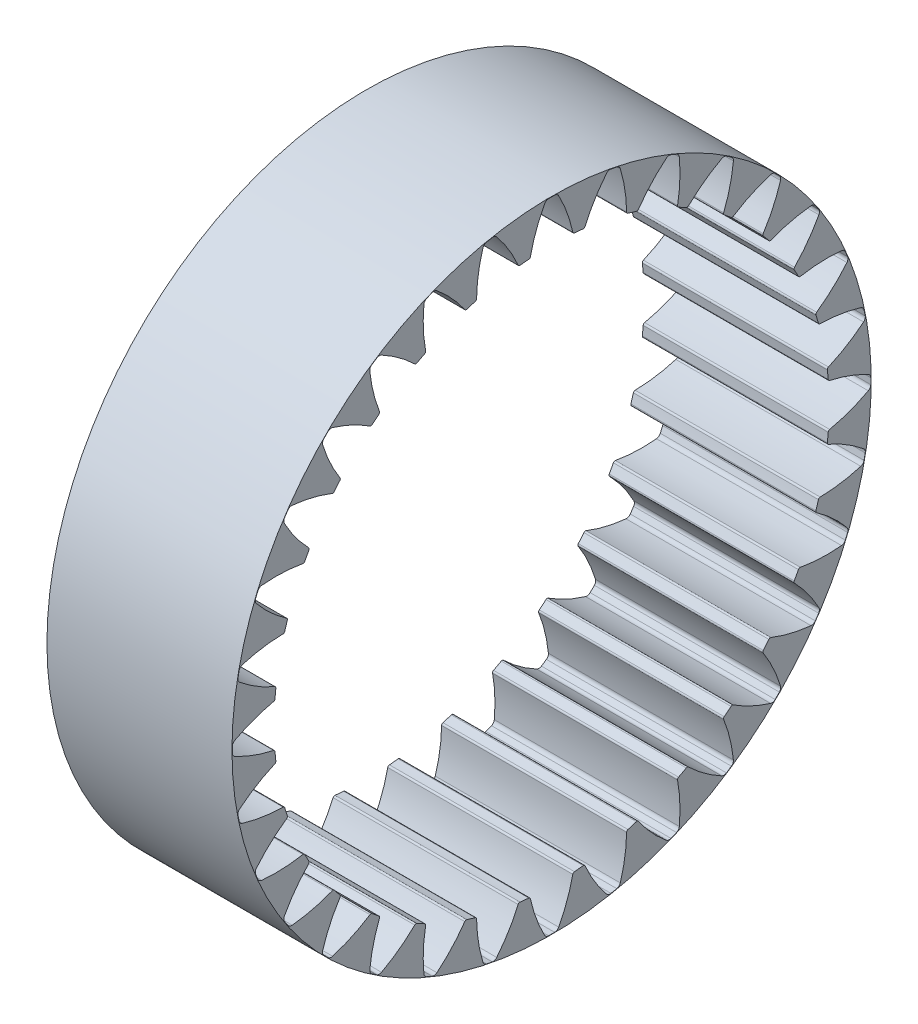
SolidWorks part; units mm, degrees
ref_plane "Plane1" through (0, 0, 0) normal (0, 0, 1) x (1, 0, 0)
ref_plane "Plane2" through (0, 0, 0) normal (0, 1, 0) x (1, 0, 0)
ref_plane "Plane3" through (0, 0, 0) normal (1, 0, 0) x (0, 0, -1)
sketch "HoldingSke" plane through (0, 0, 0) normal (0, 1, 0) x (1, 0, 0)
  line L0 (0, 0) -> (0.848, -0.5299)
  line L1 (-15, 0) -> (100, 0) construction
  line L2 (0, 0) -> (-2.1039, 2.3779)
  line L3 (0, 0) -> (-11.863, 4.5341)
  line L4 (0, 0) -> (7.3237, 4.5764)
  line L5 (0, 0) -> (-23.7986, -8.8762)
  line L6 (0, 0) -> (-10.5278, -7.1032)
  line L7 (-2.1039, 2.3779) -> (3.3635, 27.1825)
  line L8 (-76.2, 3.3779) -> (-54.61, 3.3779)
  line L9 (-67.7845, 28.3722) -> (-49.3413, 33.142)
  line L10 (-76.2, 71.12) -> (104.1128, 71.12)
  line L11 (0, 0) -> (-10, 0)
  line L12 (-76.2, 101.6) -> (-76.162, 101.6)
  line L13 (24.9733, 27.94) -> (52.9518, 28.4284)
  line L14 (24.9733, 27.94) -> (24.9743, 27.94)
  line L15 (24.9733, 27.94) -> (100.4006, 29.5858)
  circle A0 centre (0, 0) radius 12.5
  circle A1 centre (0, 0) radius 12.7
  circle A2 centre (0, 0) radius 12.7
  dimension "Num_teeth" = 32
  dimension "Pitch_radius" = 180.3128
  dimension "Width" = 10
sketch "BasProSke" plane through (0, 0, 0) normal (0, 1, 0) x (1, 0, 0)
  line L0 (-10, 0) -> (60, 0) construction
  line L1 (0, 15) -> (0, 17.2764)
  line L2 (0, 15) -> (10, 15)
  line L3 (10, 15) -> (10, 17.2764)
  line L4 (10, 17.2764) -> (0, 17.2764)
  dimension "Thickness" = 10
  dimension "Diameter" = 34.5528
revolve "Base-Revolve" add sketch "BasProSke" angle 360 about L0
sketch "TooCutSke" plane through (0, 0, 0) normal (1, 0, 0) x (0, 0, -1)
  line L3 (0.8801, 15.9758) -> (0.8801, 53.6633) construction
  line L4 (0, 0) -> (0, 59.563) construction
  line L5 (0, 0) -> (-6.6973, 67.9985) construction
  line L6 (-6.6771, 13.3511) -> (36.2941, 17.5834) construction
  circle A0 centre (0, 0) radius 16 construction
  circle A1 centre (0, 0) radius 17.251 construction
  circle A2 centre (0, 0) radius 13.9413 construction
  circle A3 centre (0, 0) radius 14.9746 construction
  arc A4 (1.1657, 14.9292) -> (0.3095, 17.2482) centre (-6.6771, 13.3511) ccw
  arc A5 (1.1657, 14.9292) -> (-1.1657, 14.9292) centre (0, 0) ccw
  arc A6 (0.3095, 17.2482) -> (-0.3095, 17.2482) centre (0, 0) ccw
  arc A7 (-0.3095, 17.2482) -> (-1.1657, 14.9292) centre (6.6771, 13.3511) ccw
extrude "ToothCut" cut sketch "TooCutSke" along normal through all
fillet "Breaks" radius 0.1 2 edges at (5, 14.955, 1.1605) (5, 14.955, -1.1605)
fillet "RootFillets" radius 0.251 2 edges at (5, 17.2482, -0.3095) (5, 17.2482, 0.3095)
pattern_circular "TeethCuts" count 32 every 11.25 about axis through (-10, 0, 0) along (1, 0, 0) of "RootFillets", "Breaks", "ToothCut"
equation "' \"Module@HoldingSke\" = 6.35"
equation "' \"Num_teeth@HoldingSke\" = 24"
equation "' \"Ap@HoldingSke\" =  14.5"
equation "' \"Ap@HoldingSke\" = 14.5"
equation "' \"Width@HoldingSke\" = 12"
equation "' \"Diameter@HoldingSke\" = 8 * 25.4"
equation "' \"Show_teeth@HoldingSke\" = 100"
equation "' \"Backlash@HoldingSke\" = 0.009 * 25.4"
equation "' \"Addendum_fac@HoldingSke\" = 1.0"
equation "' \"Dedendum_fac@HoldingSke\" = 1.25"
equation "' \"Dedendum_add@HoldingSke\" = 0.00005 * 25.4"
equation "' \"Clearance_fac@HoldingSke\" = 0.25"
equation "\"Pitch@HoldingSke\" = 1 / \"Module@HoldingSke\" "
equation "\"Overcut_dia@TooCutSke\" = (\"Num_teeth@HoldingSke\" - 2 * \"Addendum_fac@HoldingSke\") / \"Pitch@HoldingSke\" - 0.002 * 25.4"
equation "\"Pitch_dia@TooCutSke\" = \"Num_teeth@HoldingSke\" / \"Pitch@HoldingSke\""
equation "\"Base_dia@TooCutSke\" = \"Num_teeth@HoldingSke\" / \"Pitch@HoldingSke\" * cos((\"Ap@HoldingSke\"  * 3.14159265 / 180)) * 0.90"
equation "\"Root_dia@TooCutSke\" = \"Num_teeth@HoldingSke\"  / \"Pitch@HoldingSke\" + 2 *  \"Dedendum_fac@HoldingSke\"/ \"Pitch@HoldingSke\" + \"Dedendum_add@HoldingSke\" * 2"
equation "\"Half_ang@TooCutSke\" = 180 / \"Num_teeth@HoldingSke\""
equation "\"Half_CT@TooCutSke\" = \"Num_teeth@HoldingSke\" / \"Pitch@HoldingSke\" * sin((3.14159265 / 2 / \"Num_teeth@HoldingSke\")) / 2 + 10 * \"Backlash@HoldingSke\" / 4"
equation "\"Flank_rad@TooCutSke\" = \"Num_teeth@HoldingSke\" / \"Pitch@HoldingSke\" / 4"
equation "\"Radius@RootFillets\"= \"Clearance_fac@HoldingSke\" / \"Pitch@HoldingSke\" + \"Dedendum_add@HoldingSke\""
equation "\"Break_rad@Breaks\" = 0.02 / \"Pitch@HoldingSke\" * 5"
equation "\"Num_teeth@TeethCuts\" = int( \"Show_teeth@HoldingSke\" ) + 1"
equation "\"Num_teeth@TeethCuts\" = ((sgn( \"Num_teeth@TeethCuts\" - \"Num_teeth@HoldingSke\" )-1)*( \"Num_teeth@TeethCuts\" - \"Num_teeth@HoldingSke\" ))/-2+ \"Num_teeth@HoldingSke\""
equation "\"Num_teeth@TeethCuts\" = ((sgn( \"Num_teeth@TeethCuts\" - 2.0)+1)*( \"Num_teeth@TeethCuts\" - 2.0))/2 +2.0"
equation "\"Angle@TeethCuts\" = 360.0 / \"Num_teeth@HoldingSke\""
equation "\"Diameter@BasProSke\" = \"Num_teeth@HoldingSke\"  / \"Pitch@HoldingSke\" + 2 *  \"Dedendum_fac@HoldingSke\"/ \"Pitch@HoldingSke\" + \"Dedendum_add@HoldingSke\" * 2 + 0.002 * 25.4"
equation "\"Diameter@BasProSke\" = ((sgn( \"Diameter@BasProSke\"  - \"Diameter@HoldingSke\" )+1)*( \"Diameter@BasProSke\"  - \"Diameter@HoldingSke\" ))/2 + \"Diameter@HoldingSke\""
equation "\"Inside_diameter@BasProSke\" =  (\"Num_teeth@HoldingSke\" - 2 * \"Addendum_fac@HoldingSke\") / \"Pitch@HoldingSke\" "
equation "\"Thickness@BasProSke\"  = \"Width@HoldingSke\""
